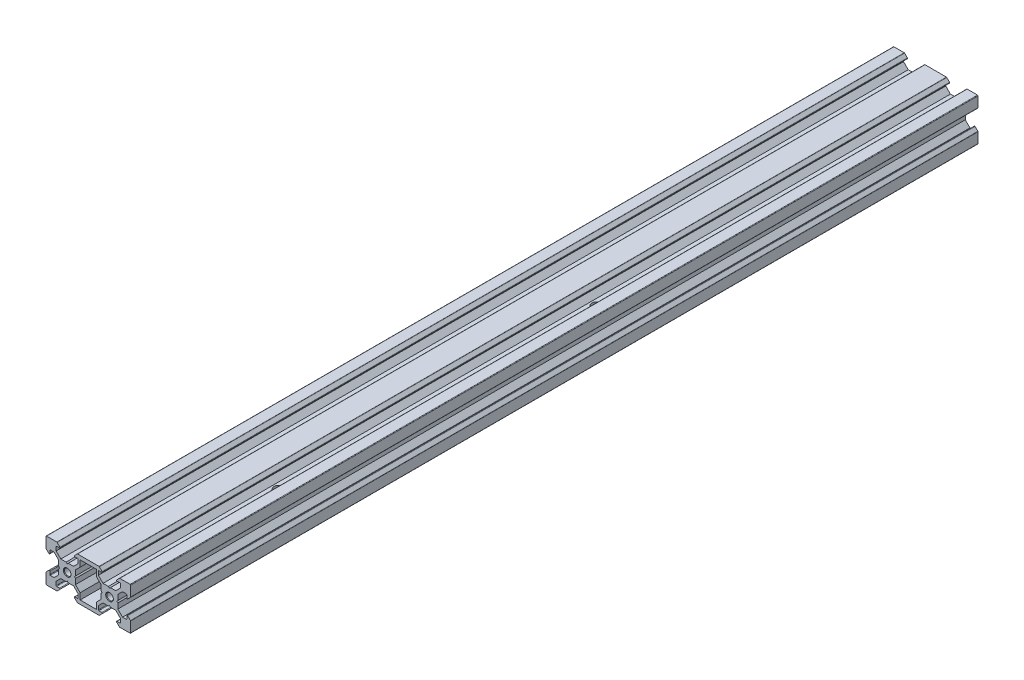
SolidWorks part; units mm, degrees
ref_plane "Alzado" through (0, 0, 0) normal (0, 0, 1) x (1, 0, 0)
ref_plane "Planta" through (0, 0, 0) normal (0, 1, 0) x (1, 0, 0)
ref_plane "Vista lateral" through (0, 0, 0) normal (1, 0, 0) x (0, 0, -1)
sketch "Croquis1" plane through (0, 0, 0) normal (0, 0, 1) x (1, 0, 0)
  line L0 (-10.0414, 10) -> (-10.0414, 8.2) construction
  line L1 (-13.8828, 8.2) -> (-6.2, 8.2)
  line L2 (-13.8828, -8.2) -> (-6.2, -8.2)
  line L4 (-4.8096, 9.9268) -> (-3.5096, 8.6268)
  line L5 (-3.6864, 8.2) -> (-5.0429, 8.2)
  line L6 (-5.2929, 7.95) -> (-5.2929, 6.2)
  line L13 (-14.8728, 8.2) -> (-16.6, 8.2)
  line L14 (-5.2929, 6.2) -> (-3.0929, 4)
  line L15 (-3.0929, 4) -> (-0.5828, 4)
  line L16 (-16.0828, 0.5) -> (-16.5828, 0)
  line L17 (-16.0828, 3.0101) -> (-16.0828, 0.5)
  line L18 (-13.8828, 5.2101) -> (-16.0828, 3.0101)
  line L19 (-13.8828, 8.2) -> (-13.8828, 5.2101)
  line L23 (-16.0828, -3.0101) -> (-16.0828, -0.5)
  line L24 (-16.0828, -0.5) -> (-16.5828, 0)
  line L25 (-13.8828, -5.2101) -> (-16.0828, -3.0101)
  line L26 (-13.8828, -8.2) -> (-13.8828, -5.2101)
  line L29 (-0.5828, 4) -> (-0.0828, 3.5)
  line L30 (-0.0828, 3.5) -> (0.4172, 4)
  line L31 (0.4172, 4) -> (2.9272, 4)
  line L32 (2.9272, 4) -> (5.1272, 6.2)
  line L33 (5.1272, 6.2) -> (5.1272, 7.95)
  line L34 (4.8772, 8.2) -> (3.5207, 8.2)
  line L35 (3.3439, 8.6268) -> (4.6439, 9.9268)
  line L36 (4.8207, 10) -> (9.6672, 10)
  line L37 (9.9172, 9.75) -> (9.9172, 4.9036)
  line L38 (9.8439, 4.7268) -> (8.5439, 3.4268)
  line L39 (8.1172, 3.6036) -> (8.1172, 4.9601)
  line L40 (7.8672, 5.2101) -> (6.1172, 5.2101)
  line L41 (6.1172, 5.2101) -> (3.9172, 3.0101)
  line L42 (3.9172, 3.0101) -> (3.9172, 0.5)
  line L43 (3.9172, 0.5) -> (3.4172, 0)
  line L44 (3.4172, 0) -> (3.9172, -0.5)
  line L45 (3.9172, -0.5) -> (3.9172, -3.0101)
  line L46 (3.9172, -3.0101) -> (6.1172, -5.2101)
  line L47 (6.1172, -5.2101) -> (7.8672, -5.2101)
  line L48 (8.1172, -4.9601) -> (8.1172, -3.6036)
  line L49 (8.5439, -3.4268) -> (9.8439, -4.7268)
  line L50 (9.9172, -4.9036) -> (9.9172, -9.75)
  line L51 (9.6672, -10) -> (4.8207, -10)
  line L52 (4.6439, -9.9268) -> (3.3439, -8.6268)
  line L53 (3.5207, -8.2) -> (4.8772, -8.2)
  line L54 (5.1272, -7.95) -> (5.1272, -6.2)
  line L55 (5.1272, -6.2) -> (2.9272, -4)
  line L56 (2.9272, -4) -> (0.4172, -4)
  line L57 (0.4172, -4) -> (-0.0828, -3.5)
  line L58 (-0.0828, -3.5) -> (-0.5828, -4)
  line L59 (-0.5828, -4) -> (-3.0929, -4)
  line L60 (-3.0929, -4) -> (-5.2929, -6.2)
  line L61 (-5.2929, -6.2) -> (-5.2929, -7.95)
  line L62 (-5.0429, -8.2) -> (-3.6864, -8.2)
  line L63 (-3.5096, -8.6268) -> (-4.8096, -9.9268)
  line L64 (-6.2, -8.2) -> (-6.2, -5.2101)
  line L65 (-6.2, -5.2101) -> (-4, -3.0101)
  line L66 (-4, -3.0101) -> (-4, -0.5)
  line L67 (-4, -0.5) -> (-3.5, 0)
  line L68 (-4, 0.5) -> (-3.5, 0)
  line L69 (-4, 3.0101) -> (-4, 0.5)
  line L70 (-6.2, 5.2101) -> (-4, 3.0101)
  line L71 (-6.2, 8.2) -> (-6.2, 5.2101)
  line L164 (-26.2, 5.2101) -> (-24, 3.0101)
  line L165 (-24, 3.0101) -> (-24, 0.5)
  line L166 (-24, 0.5) -> (-23.5, 0)
  line L167 (-23.5, 0) -> (-24, -0.5)
  line L168 (-24, -0.5) -> (-24, -3.0101)
  line L169 (-24, -3.0101) -> (-26.2, -5.2101)
  line L170 (-26.2, -5.2101) -> (-27.95, -5.2101)
  line L171 (-28.2, -4.9601) -> (-28.2, -3.6036)
  line L172 (-28.6268, -3.4268) -> (-29.9268, -4.7268)
  line L173 (-30, -4.9036) -> (-30, -9.75)
  line L174 (-29.75, -10) -> (-24.9036, -10)
  line L175 (-24.7268, -9.9268) -> (-23.4268, -8.6268)
  line L176 (-23.6036, -8.2) -> (-24.9601, -8.2)
  line L177 (-25.2101, -7.95) -> (-25.2101, -6.2)
  line L178 (-25.2101, -6.2) -> (-23.0101, -4)
  line L179 (-23.0101, -4) -> (-20.5, -4)
  line L180 (-20.5, -4) -> (-20, -3.5)
  line L181 (-20, -3.5) -> (-19.5, -4)
  line L182 (-19.5, -4) -> (-16.9899, -4)
  line L183 (-16.9899, -4) -> (-14.7899, -6.2)
  line L184 (-14.7899, -6.2) -> (-14.7899, -7.95)
  line L185 (-15.0399, -8.2) -> (-16.3964, -8.2)
  line L186 (-16.5732, -8.6268) -> (-15.2732, -9.9268)
  line L187 (-15.0964, -10) -> (-4.9864, -10)
  line L228 (-4.9864, 10) -> (-15.0964, 10)
  line L229 (-15.2732, 9.9268) -> (-16.5732, 8.6268)
  line L230 (-16.3964, 8.2) -> (-15.0399, 8.2)
  line L231 (-14.7899, 7.95) -> (-14.7899, 6.2)
  line L232 (-14.7899, 6.2) -> (-16.9899, 4)
  line L233 (-16.9899, 4) -> (-19.5, 4)
  line L234 (-19.5, 4) -> (-20, 3.5)
  line L235 (-20, 3.5) -> (-20.5, 4)
  line L236 (-20.5, 4) -> (-23.0101, 4)
  line L237 (-23.0101, 4) -> (-25.2101, 6.2)
  line L238 (-25.2101, 6.2) -> (-25.2101, 7.95)
  line L239 (-24.9601, 8.2) -> (-23.6036, 8.2)
  line L240 (-23.4268, 8.6268) -> (-24.7268, 9.9268)
  line L241 (-24.9036, 10) -> (-29.75, 10)
  line L242 (-30, 9.75) -> (-30, 4.9036)
  line L243 (-29.9268, 4.7268) -> (-28.6268, 3.4268)
  line L244 (-28.2, 3.6036) -> (-28.2, 4.9601)
  line L245 (-27.95, 5.2101) -> (-26.2, 5.2101)
  arc A0 (-3.5096, 8.6268) -> (-3.6864, 8.2) centre (-3.6864, 8.45) cw
  arc A1 (-15.0964, 10) -> (-15.2732, 9.9268) centre (-15.0964, 9.75) ccw
  arc A2 (-15.0399, 8.2) -> (-14.7899, 7.95) centre (-15.0399, 7.95) cw
  arc A4 (-16.5732, 8.6268) -> (-16.3964, 8.2) centre (-16.3964, 8.45) ccw
  arc A6 (-14.7899, -7.95) -> (-15.0399, -8.2) centre (-15.0399, -7.95) cw
  arc A7 (-16.3964, -8.2) -> (-16.5732, -8.6268) centre (-16.3964, -8.45) ccw
  arc A8 (-15.2732, -9.9268) -> (-15.0964, -10) centre (-15.0964, -9.75) ccw
  arc A9 (-24.9601, -8.2) -> (-25.2101, -7.95) centre (-24.9601, -7.95) cw
  arc A10 (-23.4268, -8.6268) -> (-23.6036, -8.2) centre (-23.6036, -8.45) ccw
  arc A11 (-24.9036, -10) -> (-24.7268, -9.9268) centre (-24.9036, -9.75) ccw
  arc A12 (-30, -9.75) -> (-29.75, -10) centre (-29.75, -9.75) ccw
  arc A13 (-29.9268, -4.7268) -> (-30, -4.9036) centre (-29.75, -4.9036) ccw
  arc A14 (-28.2, -3.6036) -> (-28.6268, -3.4268) centre (-28.45, -3.6036) ccw
  arc A15 (-27.95, -5.2101) -> (-28.2, -4.9601) centre (-27.95, -4.9601) cw
  arc A16 (-24.7268, 9.9268) -> (-24.9036, 10) centre (-24.9036, 9.75) ccw
  arc A17 (-23.6036, 8.2) -> (-23.4268, 8.6268) centre (-23.6036, 8.45) ccw
  arc A18 (-25.2101, 7.95) -> (-24.9601, 8.2) centre (-24.9601, 7.95) cw
  arc A19 (-28.2, 4.9601) -> (-27.95, 5.2101) centre (-27.95, 4.9601) cw
  arc A20 (-28.6268, 3.4268) -> (-28.2, 3.6036) centre (-28.45, 3.6036) ccw
  arc A21 (-30, 4.9036) -> (-29.9268, 4.7268) centre (-29.75, 4.9036) ccw
  arc A22 (-29.75, 10) -> (-30, 9.75) centre (-29.75, 9.75) ccw
  arc A23 (-5.0429, 8.2) -> (-5.2929, 7.95) centre (-5.0429, 7.95) ccw
  arc A24 (5.1272, 7.95) -> (4.8772, 8.2) centre (4.8772, 7.95) ccw
  arc A25 (3.5207, 8.2) -> (3.3439, 8.6268) centre (3.5207, 8.45) cw
  arc A26 (4.6439, 9.9268) -> (4.8207, 10) centre (4.8207, 9.75) cw
  arc A27 (9.6672, 10) -> (9.9172, 9.75) centre (9.6672, 9.75) cw
  arc A28 (9.9172, 4.9036) -> (9.8439, 4.7268) centre (9.6672, 4.9036) cw
  arc A29 (8.5439, 3.4268) -> (8.1172, 3.6036) centre (8.3672, 3.6036) cw
  arc A30 (8.1172, 4.9601) -> (7.8672, 5.2101) centre (7.8672, 4.9601) ccw
  arc A31 (7.8672, -5.2101) -> (8.1172, -4.9601) centre (7.8672, -4.9601) ccw
  arc A32 (8.1172, -3.6036) -> (8.5439, -3.4268) centre (8.3672, -3.6036) cw
  arc A33 (9.8439, -4.7268) -> (9.9172, -4.9036) centre (9.6672, -4.9036) cw
  arc A34 (9.9172, -9.75) -> (9.6672, -10) centre (9.6672, -9.75) cw
  arc A35 (4.8207, -10) -> (4.6439, -9.9268) centre (4.8207, -9.75) cw
  arc A36 (3.3439, -8.6268) -> (3.5207, -8.2) centre (3.5207, -8.45) cw
  arc A37 (4.8772, -8.2) -> (5.1272, -7.95) centre (4.8772, -7.95) ccw
  arc A38 (-5.2929, -7.95) -> (-5.0429, -8.2) centre (-5.0429, -7.95) ccw
  arc A39 (-3.6864, -8.2) -> (-3.5096, -8.6268) centre (-3.6864, -8.45) cw
  arc A40 (-4.8096, -9.9268) -> (-4.9864, -10) centre (-4.9864, -9.75) cw
  arc A41 (-4.9864, 10) -> (-4.8096, 9.9268) centre (-4.9864, 9.75) cw
  point P47 (-10.0414, -8.2)
  point P134 (-10.0414, 8.2)
  dimension "D1" = 0.25
extrude "Saliente-Extruir1" add sketch "Croquis1" along normal blind 200 and the other way blind 200 contours A41 L228 L1 L71 L70 L69 L68 L67 L66 L65 L64 L2 L26 L25 L23 L24 L16 L17 L18 L19 A1 L229 A4 L13 A2 L231 L232 L233 L234 L235 L236 L237 L238 A18 L239 A17 L240 A16 L241 A22 L242 A21 L243 A20 L244 region at (-4.4753, 8.9611, 0)
sketch "Croquis4" plane through (0, 0, 200) normal (0, 0, 1) x (1, 0, 0)
  line L0 (-24.6708, 0) -> (6.8007, 0) construction
  line L1 (-20, 3.5) -> (-20, 0) construction
  circle A0 centre (-20, 0) radius 1.5693
  circle A1 centre (0, 0) radius 1.5693
extrude "Cortar-Extruir1" cut sketch "Croquis4" against normal through all
chamfer "Chaflán1" distance 0.25 angle 45 4 edges at (-18.4307, 0, -200) (1.5693, 0, -200) (1.5693, 0, 200) (-18.4307, 0, 200)
sketch "Croquis9" plane through (0, 10, 0) normal (0, 1, 0) x (1, 0, 0)
  line L0 (-0.0828, 159) -> (-0.0828, -200) construction
  line L1 (-4.9864, -200) -> (-15.0964, -200) construction
  circle A0 centre (-0.0828, -120) radius 2.25
  circle A1 centre (-0.0828, 30) radius 2.25
  point P0 (-0.0828, -120)
  point P1 (-0.0828, 30)
  dimension "D3" = 4.5
  dimension "D1" = 80
  dimension "D2" = 150
extrude "Cortar-Extruir2" cut sketch "Croquis9" against normal through all
